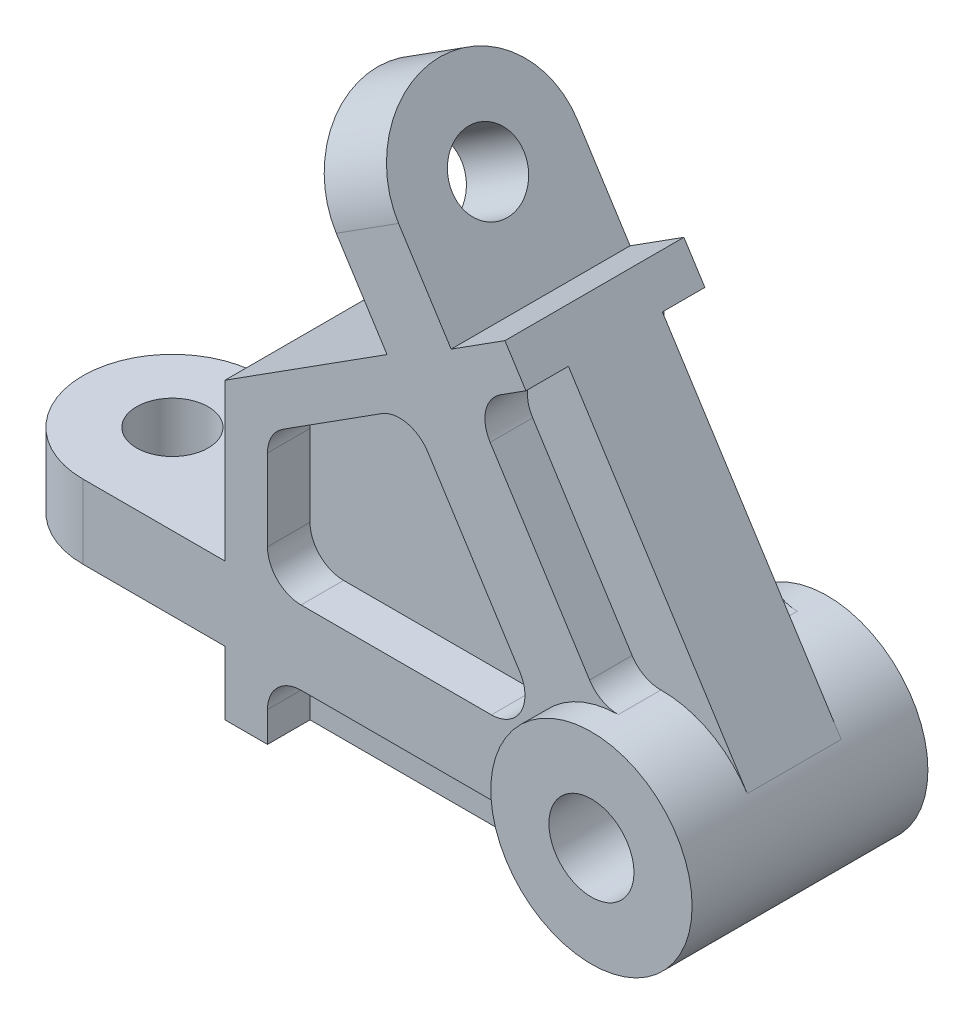
SolidWorks part; units mm, degrees
material "AISI 1020"
ref_plane "Front Plane" through (0, 0, 0) normal (0, 0, 1) x (1, 0, 0)
ref_plane "Top Plane" through (0, 0, 0) normal (0, 1, 0) x (1, 0, 0)
ref_plane "Right Plane" through (0, 0, 0) normal (1, 0, 0) x (0, 0, -1)
sketch "Sketch1" plane through (0, 0, 0) normal (0, 0, 1) x (1, 0, 0)
  line L0 (18.9763, 12.0892) -> (-25.6851, 82.1936)
  line L1 (-25.6851, 82.1936) -> (-37.7034, 74.537)
  line L2 (-37.7034, 74.537) -> (-60.2045, 109.8567)
  line L3 (-60.2045, 109.8567) -> (-74.1204, 100.9912)
  line L4 (-74.1204, 100.9912) -> (-52.0339, 66.3222)
  line L5 (-52.0339, 66.3222) -> (-88.25, 43.25)
  line L6 (-88.25, 43.25) -> (-88.25, 8.25)
  line L7 (-88.25, 8.25) -> (-140, 8.25)
  line L8 (-140, 8.25) -> (-140, -8.25)
  line L9 (-140, -8.25) -> (-88.25, -8.25)
  line L10 (-88.25, -8.25) -> (-88.25, -22.5)
  line L11 (-88.25, -22.5) -> (0, -22.5)
  line L12 (0, 0) -> (-143.2915, 0) construction
  line L13 (0, 0) -> (-77.5947, 121.7993) construction
  line L14 (-20.9952, 74.832) -> (-26.6881, 71.2052)
  line L15 (-28.9838, 60.85) -> (-6.7609, 25.9671)
  line L17 (-42.8998, 51.9846) -> (-22.383, 19.7797)
  line L18 (-28.7085, 8.25) -> (-71.25, 8.25)
  line L19 (-78.75, 15.75) -> (-78.75, 33.9235)
  line L20 (-75.2797, 40.2489) -> (-53.2549, 54.2803)
  line L21 (-78.75, -22.5) -> (-78.75, -15.75)
  line L22 (-71.25, -8.25) -> (-25.5331, -8.25)
  circle A0 centre (0, 0) radius 9.5
  circle A1 centre (0, 0) radius 22.5
  arc A2 (-6.7609, 25.9671) -> (-0.3266, 22.4976) centre (-0.4355, 29.9968) ccw
  arc A3 (-78.75, 33.9235) -> (-75.2797, 40.2489) centre (-71.25, 33.9235) cw
  arc A4 (-22.383, 19.7797) -> (-28.7085, 8.25) centre (-28.7085, 15.75) cw
  arc A5 (-42.8998, 51.9846) -> (-53.2549, 54.2803) centre (-49.2252, 47.9548) ccw
  arc A6 (-26.6881, 71.2052) -> (-28.9838, 60.85) centre (-22.6584, 64.8798) ccw
  arc A7 (-25.5331, -8.25) -> (-19.1498, -11.8125) centre (-25.5331, -15.75) cw
  arc A8 (-78.75, -15.75) -> (-71.25, -8.25) centre (-71.25, -15.75) cw
  arc A9 (-71.25, 8.25) -> (-78.75, 15.75) centre (-71.25, 15.75) cw
  point P6 (-140, 0)
  point P19 (-67.1625, 105.4239)
  point P25 (0, 0)
  point P31 (0, 0)
  point P33 (-18.3275, -13.0519)
  point P34 (-31.6942, 78.3653)
  point P35 (-23.8417, 73.0186)
  point P36 (-19.5347, 22.8207)
  point P37 (-6.9259, 26.6111)
  point P48 (-70.6051, 9.3438)
  point P49 (-27.9166, 7)
  point P56 (-48.1915, 51.3087)
  point P57 (-34.0393, 7)
  point P58 (-153.7035, 7)
  point P59 (-83.2373, 113.3841)
  point P60 (-45.6758, 66.1976)
  point P61 (-8.4898, 23.969)
  point P62 (0, 0)
  point P63 (0, 0)
  point P64 (-4.1037, 22.1226)
  point P65 (-25.35, -11.596)
  point P66 (-71.6457, -7)
  dimension "D1" = 45
  dimension "D2" = 19
  dimension "D7" = 7.5
  dimension "D8" = 7.5
  dimension "D11" = 7.5
  dimension "D12" = 7.5
  dimension "D3" = 16.5
  dimension "D4" = 9.5
  dimension "D5" = 9.5
  dimension "D6" = 16.5
  dimension "D9" = 9.5
  dimension "D10" = 35
  dimension "D13" = 88.25
  dimension "D14" = 140
  dimension "D15" = 125
  dimension "D16" = 57.5
extrude "Boss-Extrude1" add sketch "Sketch1" along normal mid plane 52.7 contours A1 A0 region at (20.9901, 6.1181, 0)
extrude "Boss-Extrude2" add sketch "Sketch1<3>" along normal mid plane 40 contours L21 A8 L22 A7 A1 A2 L15 A6 L14 L0 L1 L2 L3 L4 L5 L6 L7 L8 L9 L10 L11 L18 A9 L19 A3 L20 A5 L17 A4 region at (-24.8756, 74.6415, 0)
sketch "Sketch1<3>" plane through (0, 0, 0) normal (0, 0, 1) x (1, 0, 0) same geometry as "Sketch1"
extrude "Boss-Extrude3" add sketch "Sketch1<4>" along normal mid plane 21 contours A9 L18 A4 L17 A5 L20 A3 L19 | L14 A6 L15 A2 A1 L0 | A8 L21 L11 A1 A7 L22 region at (-10.4608, 45.8297, 0) region at (-46.4653, -15.772, 0) region at (-52.2788, 27.4699, 0)
sketch "Sketch1<4>" plane through (0, 0, 0) normal (0, 0, 1) x (1, 0, 0) same geometry as "Sketch1"
sketch "Sketch2" plane through (0, 0, 0) normal (0, 1, 0) x (1, 0, 0)
  line L0 (0, 0) -> (0, -20)
  line L1 (0, -20) -> (-120, -20)
  line L2 (-88.25, -20) -> (-140, -20) construction
  line L3 (-88.25, 20) -> (-140, 20) construction
  line L4 (-120, 20) -> (0, 20)
  line L5 (0, 20) -> (0, 0)
  line L6 (-140, -20) -> (-120, -20)
  line L7 (-17, -20) -> (-17, 20)
  line L8 (-140, -20) -> (-140, 20) construction
  line L9 (-140, -20) -> (-140, 20)
  line L10 (-140, 20) -> (-120, 20)
  arc A0 (-120, -20) -> (-120, 20) centre (-120, 0) cw
  circle A1 centre (-120, 0) radius 8
  point P13 (0, 0)
  point P17 (-140, 0)
  dimension "D1" = 16
  dimension "D3" = 20
  dimension "D2" = 120
  dimension "D4" = 17
extrude "Cut-Extrude1" cut sketch "Sketch2" against normal through all both and the other way through all contours L6 A0 L9 | L9 A0 L10 | A1 region at (-135.5326, 0, 15.5326) region at (-135.5326, 0, -15.5326) region at (-120, 0, 0)
sketch "Sketch4" plane through (6.958, 4.4327, 0) normal (0.8434, 0.5373, 0) x (0, 0, -1)
  line L0 (0, 0) -> (0, 147.3988) construction
  line L1 (-20, 105) -> (-20, 0)
  line L2 (-20, 0) -> (20, 0)
  line L3 (20, 0) -> (20, 125)
  line L4 (20, 125) -> (-20, 125)
  line L5 (-20, 125) -> (-20, 105)
  circle A0 centre (0, 105) radius 8
  arc A1 (20, 105) -> (-20, 105) centre (0, 105) ccw
  point P5 (0, 120)
  point P13 (-20, 118.7588)
  line M2 (20, 125) -> (-20, 125)
  line M3 (-20, 125) -> (-20, 83.1219)
  dimension "D1" = 16
extrude "Cut-Extrude2" cut sketch "Sketch4" against normal through all both and the other way through all contours A1 L3 M2 | A1 L4 M3 | L0 A0 | A0 L0 region at (-49.4585, 92.9888, 3.3953) region at (-49.4585, 92.9888, -3.3953) region at (-57.8042, 106.0889, -15.5326) region at (-57.8042, 106.0889, 15.5326)
equation "\"A\" = 105"
equation "\"B\" = 16.5"
equation "\"C\"= 57.5"
equation "\"D3@Sketch1\"=\"B\""
equation "\"D6@Sketch1\"=\"B\""
equation "\"D13@Sketch1\"=120-31.75"
equation "\"D15@Sketch1\"=\"A\"+20"
equation "\"D16@Sketch1\"=\"C\""
